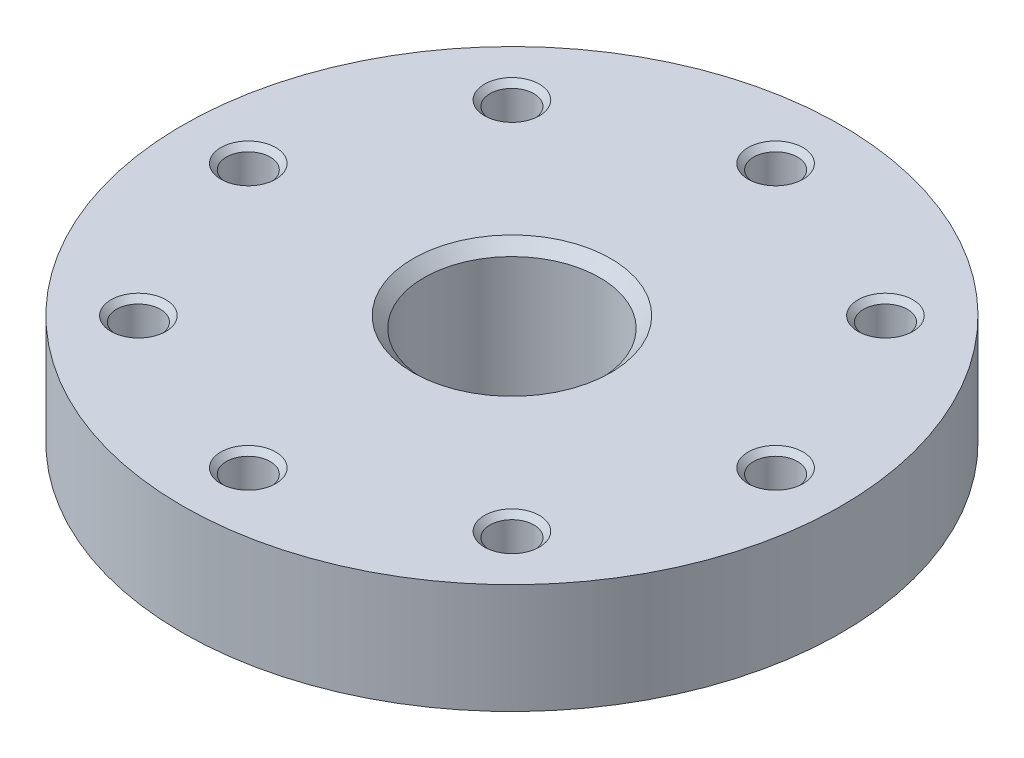
SolidWorks part; units mm, degrees
ref_plane "Front Plane" through (0, 0, 0) normal (0, 0, 1) x (1, 0, 0)
ref_plane "Top Plane" through (0, 0, 0) normal (0, 1, 0) x (1, 0, 0)
ref_plane "Right Plane" through (0, 0, 0) normal (1, 0, 0) x (0, 0, -1)
sketch "Sketch1" plane through (0, 0, 0) normal (0, 1, 0) x (1, 0, 0)
  circle A0 centre (0, 0) radius 15
extrude "Boss-Extrude1" add sketch "Sketch1" along normal blind 5
sketch "Sketch2" plane through (0, 5, 0) normal (0, 1, 0) x (1, 0, 0)
  line L0 (-12, 0) -> (12, 0) construction
  line L1 (0, -12) -> (0, 12) construction
  line L2 (-8.5, 8.5) -> (8.5, 8.5) construction
  line L3 (-8.5, 8.5) -> (-8.5, -8.5) construction
  line L4 (-8.5, -8.5) -> (8.5, -8.5) construction
  line L5 (8.5, -8.5) -> (8.5, 8.5) construction
  circle A0 centre (0, 12) radius 1
  circle A1 centre (-12, 0) radius 1
  circle A2 centre (0, -12) radius 1
  circle A3 centre (12, 0) radius 1
  circle A4 centre (-8.5, 8.5) radius 1
  circle A5 centre (-8.5, -8.5) radius 1
  circle A6 centre (8.5, 8.5) radius 1
  circle A7 centre (8.5, -8.5) radius 1
  point P5 (0, 0)
  point P9 (0, 0)
  point P16 (0, 8.5)
  point P19 (-8.5, 0)
extrude "Cut-Extrude1" cut sketch "Sketch2" against normal through all
sketch "Sketch3" plane through (0, 0, 0) normal (0, 1, 0) x (1, 0, 0)
  circle A0 centre (0, 0) radius 6
extrude "Boss-Extrude2" add sketch "Sketch3" against normal blind 1.5
sketch "Sketch4" plane through (0, -1.5, 0) normal (0, -1, 0) x (1, 0, 0)
  circle A0 centre (0, 0) radius 1.5
extrude "Cut-Extrude2" cut sketch "Sketch4" against normal blind 1.5
chamfer "Chamfer5" distance 0.25 angle 45 16 edges at (-12, 0, 1) (-8.5, 0, -7.5) (0, 0, -11) (8.5, 0, -7.5) (12, 0, 1) (8.5, 0, 9.5) (0, 0, 13) (-8.5, 0, 9.5) (8.5, 5, -7.5) (0, 5, -11) (-8.5, 5, -7.5) (-12, 5, 1) (-8.5, 5, 9.5) (0, 5, 13) (8.5, 5, 9.5) (12, 5, 1)
sketch "Sketch5" plane through (0, 5, 0) normal (0, 1, 0) x (1, 0, 0)
  circle A1 centre (0, 0) radius 4
extrude "Cut-Extrude3" cut sketch "Sketch5" against normal blind 6
chamfer "Chamfer7" distance 0.5 angle 45 1 edges at (0, 5, 4)
